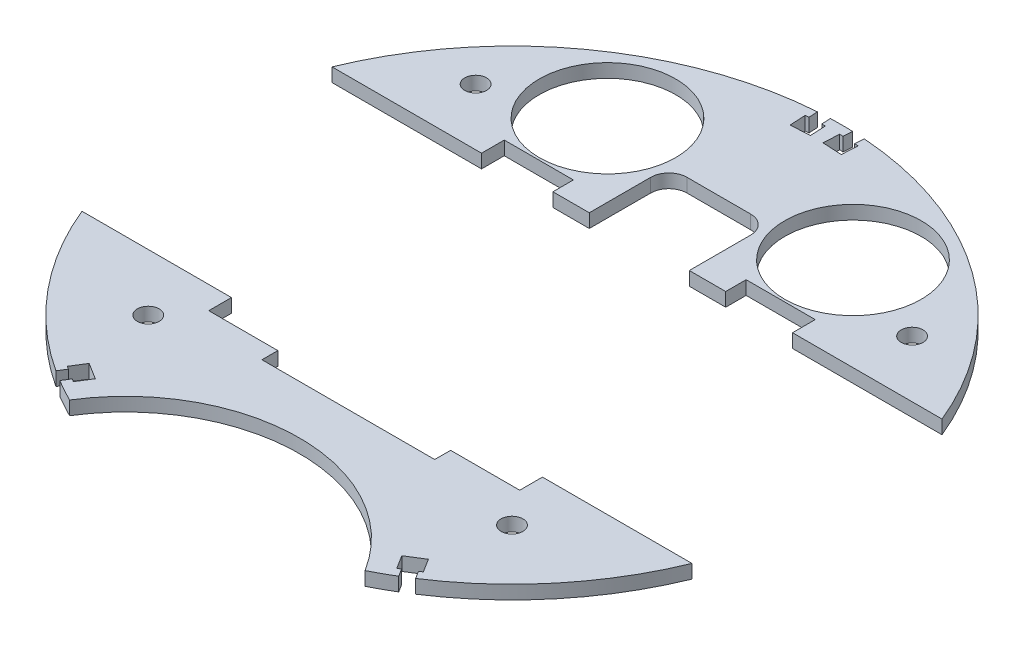
SolidWorks part; units mm, degrees
material "ABS"
ref_plane "Front Plane" through (0, 0, 0) normal (0, 0, 1) x (1, 0, 0)
ref_plane "Top Plane" through (0, 0, 0) normal (0, 1, 0) x (1, 0, 0)
ref_plane "Right Plane" through (0, 0, 0) normal (1, 0, 0) x (0, 0, -1)
sketch "Sketch1" plane through (0, 0, 0) normal (0, 1, 0) x (1, 0, 0)
  line L0 (0, -85) -> (-32.4891, -64.8129) construction
  line L1 (0, -85) -> (0, 0) construction
  arc A0 (32.4891, -64.8129) -> (-32.4891, -64.8129) centre (0, 0) ccw
  arc A1 (32.4891, -64.8129) -> (-32.4891, -64.8129) centre (0, -85) ccw
  dimension "D1" = 145
  dimension "D2" = 76.5
  dimension "D3" = 85
extrude "Boss-Extrude1" add sketch "Sketch1" along normal blind 3
sketch "solenoid placement" plane through (0, 3, 0) normal (0, 1, 0) x (1, 0, 0)
  line L4 (-19, -36) -> (19, -36)
  line L5 (-19, -36) -> (19, -36)
  line L6 (19, -36) -> (19, 28)
  line L7 (19, -36) -> (19, 28)
  line L8 (19, 28) -> (-19, 28)
  line L9 (19, 28) -> (-19, 28)
  line L10 (-19, 28) -> (-19, -36)
  line L11 (-19, 28) -> (-19, -36)
  circle A1 centre (0, 0) radius 72.5 construction
  arc A2 (32.4891, -64.8129) -> (-32.4891, -64.8129) centre (0, 0) ccw construction
  dimension "D1" = 0
extrude "Cut-Extrude1" cut sketch "solenoid placement" against normal through all
sketch "Sketch3" plane through (0, 3, 0) normal (0, 1, 0) x (1, 0, 0)
  circle A1 centre (27, 48) radius 12
  circle A2 centre (-27, 48) radius 12
  dimension "D1" = 24
extrude "Cut-Extrude3" cut sketch "Sketch3" against normal through all
sketch "Sketch4" plane through (0, 3, 0) normal (0, 1, 0) x (1, 0, 0)
  circle A2 centre (40, -40) radius 2.4
  circle A3 centre (40, -40) radius 2.4
  circle A4 centre (-40, -40) radius 2.4
  circle A5 centre (-40, -40) radius 2.4
  circle A6 centre (48, 40) radius 2.4
  circle A7 centre (48, 40) radius 2.4
  circle A8 centre (-48, 40) radius 2.4
  circle A12 centre (-48, 40) radius 2.4
  dimension "D1" = 0
  dimension "D2" = 0
  dimension "D3" = 0
  dimension "D4" = 0
extrude "Cut-Extrude4" cut sketch "Sketch4" against normal through all
sketch "Sketch2" plane through (0, 3, 0) normal (0, 1, 0) x (1, 0, 0)
  line L0 (0, 0) -> (0, 72.5) construction
  line L1 (34.2, -27.5) -> (34.2, -32.5)
  line L2 (67.082, -27.5) -> (34.2, -27.5)
  line L3 (34.2, 27.5) -> (67.082, 27.5)
  line L4 (34.2, 32.5) -> (34.2, 27.5)
  line L5 (22.2, 32.5) -> (34.2, 32.5)
  line L6 (19, 32.5) -> (22.2, 32.5)
  line L7 (19, -32.5) -> (19, 32.5)
  line L8 (22.2, -32.5) -> (19, -32.5)
  line L9 (-34.2, -32.5) -> (-22.2, -32.5)
  line L10 (-22.2, -32.5) -> (-19, -32.5)
  line L11 (-19, -32.5) -> (-19, 32.5)
  line L12 (-19, 32.5) -> (-22.2, 32.5)
  line L13 (-22.2, 32.5) -> (-34.2, 32.5)
  line L14 (-34.2, 32.5) -> (-34.2, 25)
  line L15 (-34.2, 25) -> (-68.0533, 25)
  line L16 (-68.0533, -25) -> (-34.2, -25)
  line L17 (-34.2, -25) -> (-34.2, -32.5)
  line L18 (-34.2, -32.5) -> (-22.2, -32.5)
  line L19 (-22.2, -32.5) -> (-19, -32.5)
  line L20 (-19, -32.5) -> (-19, 32.5)
  line L21 (-19, 32.5) -> (-22.2, 32.5)
  line L22 (-22.2, 32.5) -> (-34.2, 32.5)
  line L23 (-34.2, 32.5) -> (-34.2, 27.5)
  line L24 (-34.2, 27.5) -> (-67.082, 27.5)
  line L25 (-67.082, -27.5) -> (-34.2, -27.5)
  line L26 (-34.2, -27.5) -> (-34.2, -32.5)
  line L27 (34.2, -32.5) -> (22.2, -32.5)
  arc A0 (32.4891, -64.8129) -> (-32.4891, -64.8129) centre (0, 0) ccw construction
  arc A1 (67.082, 27.5) -> (67.082, -27.5) centre (0, 0) cw
  arc A2 (-68.0533, 25) -> (-68.0533, -25) centre (0, 0) ccw
  arc A3 (-67.082, 27.5) -> (-67.082, -27.5) centre (0, 0) ccw
  dimension "D2" = 55
  dimension "D1" = 0
extrude "Cut-Extrude2" cut sketch "Sketch2" against normal through all
sketch "Sketch5" plane through (0, 3, 0) normal (0, 1, 0) x (1, 0, 0)
  line L8 (-11, 28) -> (11, 28)
  line L9 (11, 28) -> (11, 41.5)
  line L10 (7, 45.5) -> (-7, 45.5)
  line L11 (-11, 41.5) -> (-11, 28)
  line L12 (19, 28) -> (-19, 28) construction
  arc A4 (11, 41.5) -> (7, 45.5) centre (7, 41.5) ccw
  arc A5 (-7, 45.5) -> (-11, 41.5) centre (-7, 41.5) ccw
  point P10 (0, 28)
  point P13 (0, 28)
  line M18 (-19, 28) -> (19, 28)
  dimension "D3" = 4
  dimension "D1" = 22
  dimension "D2" = 17.5
extrude "Cut-Extrude5" cut sketch "Sketch5" against normal through all contours L10 A5 L11 L9 A4 M18 region at (0, 3, -36.6073)
sketch "Sketch6" plane through (0, 3, 0) normal (0, 1, 0) x (-1, 0, 0)
  circle A1 centre (-27, -48) radius 15
  circle A2 centre (-27, -48) radius 15
  circle A3 centre (27, -48) radius 15
  circle A4 centre (27, -48) radius 15
  dimension "D1" = 0
  dimension "D2" = 0
extrude "Cut-Extrude10" cut sketch "Sketch6" against normal through all
sketch "Sketch7" plane through (0, 3, 0) normal (0, 1, 0) x (1, 0, 0)
  line L8 (-5.0378, 70.3327) -> (-5.8118, 70.2922)
  line L9 (-5.8118, 70.2922) -> (-5.6286, 66.797)
  line L10 (-5.6286, 66.797) -> (-1.3844, 67.0194)
  line L11 (-1.3844, 67.0194) -> (-1.5676, 70.5146)
  line L12 (-1.5676, 70.5146) -> (-2.3415, 70.474)
  line L13 (-2.3415, 70.474) -> (-2.4462, 72.4713)
  line L14 (-2.4462, 72.4713) -> (-5.1425, 72.33)
  line L15 (-5.1425, 72.33) -> (-5.0378, 70.3327)
  line L16 (-5.0378, 70.3327) -> (-5.8118, 70.2922)
  line L17 (-5.8118, 70.2922) -> (-5.6286, 66.797)
  line L18 (-5.6286, 66.797) -> (-1.3844, 67.0194)
  line L19 (-1.3844, 67.0194) -> (-1.5676, 70.5146)
  line L20 (-1.5676, 70.5146) -> (-2.3415, 70.474)
  line L21 (-2.3415, 70.474) -> (-2.4462, 72.4713)
  line L22 (-2.4462, 72.4713) -> (-5.1425, 72.33)
  line L23 (-5.1425, 72.33) -> (-5.0378, 70.3327)
  line L24 (5.8118, 70.2922) -> (5.0378, 70.3327)
  line L25 (5.6286, 66.797) -> (5.8118, 70.2922)
  line L26 (1.3844, 67.0194) -> (5.6286, 66.797)
  line L27 (1.5676, 70.5146) -> (1.3844, 67.0194)
  line L28 (2.3415, 70.474) -> (1.5676, 70.5146)
  line L29 (2.4462, 72.4713) -> (2.3415, 70.474)
  line L30 (5.1425, 72.33) -> (2.4462, 72.4713)
  line L31 (5.0378, 70.3327) -> (5.1425, 72.33)
  line L32 (5.8118, 70.2922) -> (5.0378, 70.3327)
  line L33 (5.6286, 66.797) -> (5.8118, 70.2922)
  line L34 (1.3844, 67.0194) -> (5.6286, 66.797)
  line L35 (1.5676, 70.5146) -> (1.3844, 67.0194)
  line L36 (2.3415, 70.474) -> (1.5676, 70.5146)
  line L37 (2.4462, 72.4713) -> (2.3415, 70.474)
  line L38 (5.1425, 72.33) -> (2.4462, 72.4713)
  line L39 (5.0378, 70.3327) -> (5.1425, 72.33)
  line L40 (38.5042, -59.072) -> (39.1614, -58.6613)
  line L41 (39.564, -60.7681) -> (38.5042, -59.072)
  line L42 (37.2743, -62.1989) -> (39.564, -60.7681)
  line L43 (36.2144, -60.5028) -> (37.2743, -62.1989)
  line L44 (35.5572, -60.9135) -> (36.2144, -60.5028)
  line L45 (33.7025, -57.9453) -> (35.5572, -60.9135)
  line L46 (37.3067, -55.6931) -> (33.7025, -57.9453)
  line L47 (39.1614, -58.6613) -> (37.3067, -55.6931)
  line L48 (38.5042, -59.072) -> (39.1614, -58.6613)
  line L49 (39.564, -60.7681) -> (38.5042, -59.072)
  line L50 (37.2743, -62.1989) -> (39.564, -60.7681)
  line L51 (36.2144, -60.5028) -> (37.2743, -62.1989)
  line L52 (35.5572, -60.9135) -> (36.2144, -60.5028)
  line L53 (33.7025, -57.9453) -> (35.5572, -60.9135)
  line L54 (37.3067, -55.6931) -> (33.7025, -57.9453)
  line L55 (39.1614, -58.6613) -> (37.3067, -55.6931)
  line L56 (-39.1614, -58.6613) -> (-38.5042, -59.072)
  line L57 (-37.3067, -55.6931) -> (-39.1614, -58.6613)
  line L58 (-33.7025, -57.9453) -> (-37.3067, -55.6931)
  line L59 (-35.5572, -60.9135) -> (-33.7025, -57.9453)
  line L60 (-36.2144, -60.5028) -> (-35.5572, -60.9135)
  line L61 (-37.2743, -62.1989) -> (-36.2144, -60.5028)
  line L62 (-39.564, -60.7681) -> (-37.2743, -62.1989)
  line L63 (-38.5042, -59.072) -> (-39.564, -60.7681)
  line L64 (-39.1614, -58.6613) -> (-38.5042, -59.072)
  line L65 (-37.3067, -55.6931) -> (-39.1614, -58.6613)
  line L66 (-33.7025, -57.9453) -> (-37.3067, -55.6931)
  line L67 (-35.5572, -60.9135) -> (-33.7025, -57.9453)
  line L68 (-36.2144, -60.5028) -> (-35.5572, -60.9135)
  line L69 (-37.2743, -62.1989) -> (-36.2144, -60.5028)
  line L70 (-39.564, -60.7681) -> (-37.2743, -62.1989)
  line L71 (-38.5042, -59.072) -> (-39.564, -60.7681)
  dimension "D1" = 0
  dimension "D2" = 0
  dimension "D3" = 0
  dimension "D4" = 0
extrude "Cut-Extrude11" cut sketch "Sketch7" against normal through all
sketch "Sketch8" plane through (0, 3, 0) normal (0, 1, 0) x (1, 0, 0)
  line L2 (7, 48.5) -> (-7, 48.5)
  line L3 (7.1569, 48.5) -> (-7.1569, 48.5)
  line L8 (-8.4675, 63.6441) -> (-1.2274, 64.0235)
  line L9 (-8.8077, 70.1352) -> (-8.4675, 63.6441)
  line L10 (-6.4702, 63.7487) -> (-0.1047, 64.0823)
  line L11 (-8.6309, 66.7627) -> (-8.5721, 65.6413)
  line L15 (8.4675, 63.6441) -> (8.8077, 70.1352)
  line L16 (1.2274, 64.0235) -> (8.4675, 63.6441)
  line L17 (8.5721, 65.6413) -> (8.6309, 66.7627)
  line L18 (0.1047, 64.0823) -> (6.4702, 63.7487)
  circle A2 centre (-27, 48) radius 18
  arc A3 (-9.1412, 50.25) -> (-18.004, 63.5907) centre (-27, 48) ccw
  circle A5 centre (27, 48) radius 18
  arc A6 (18.004, 63.5907) -> (9.1412, 50.25) centre (27, 48) ccw
  arc A8 (-4.9291, 69.325) -> (-64.3062, 26.3621) centre (0, 0) ccw
  arc A9 (-10.9431, 68.6331) -> (-17.5082, 67.2585) centre (0, 0) ccw
  arc A10 (17.5082, 67.2585) -> (10.9431, 68.6331) centre (0, 0) ccw
  arc A11 (-9.1412, 50.25) -> (-7.1569, 48.5) centre (-7.1569, 50.5) ccw
  arc A12 (9.1412, 50.25) -> (7.1569, 48.5) centre (7.1569, 50.5) cw
  arc A13 (17.5082, 67.2585) -> (18.004, 63.5907) centre (17.0044, 65.323) cw
  arc A14 (10.9431, 68.6331) -> (8.6309, 66.7627) centre (10.6282, 66.658) ccw
  arc A15 (8.5721, 65.6413) -> (6.4702, 63.7487) centre (6.5749, 65.746) cw
  arc A16 (-0.1047, 64.0823) -> (0.1047, 64.0823) centre (0, 62.0851) cw
  arc A17 (-6.4702, 63.7487) -> (-8.5721, 65.6413) centre (-6.5749, 65.746) cw
  arc A18 (-8.6309, 66.7627) -> (-10.9431, 68.6331) centre (-10.6282, 66.658) ccw
  arc A19 (-18.004, 63.5907) -> (-17.5082, 67.2585) centre (-17.0044, 65.323) cw
  dimension "D5" = 2
  dimension "D1" = 3
  dimension "D2" = 3
  dimension "D3" = 3
  dimension "D4" = 3
  dimension "D6" = 3
  dimension "D7" = 3
extrude "Cut-Extrude12" [suppressed] cut sketch "Sketch8" against normal through all and the other way through all
equation "\"smallPulleyTeeth\"= 15"
equation "\"largePulleyTeeth\"= 30"
equation "\"eighthThick\"= 3.0mm"
equation "\"sixteenthThick\"= 1.7mm"
equation "\"quarterThick\"=6.0mm"
equation "\"OD\"= 145mm"
equation "\"puckAngle\"= 60.5deg"
equation "\"D1@Sketch1\"=\"OD\""
equation "\"puckDiam\"= 76.5mm"
equation "\"D2@Sketch1\"=\"puckDiam\""
equation "\"D1@Boss-Extrude1\"=\"eighthThick\""
equation "\"axlePress\"= 5.9mm"
equation "\"press\"= 0.2mm"
equation "\"wheelClear\"= 0.3mm"
equation "\"10-32clear\"= 4.8mm"
equation "\"6-32clear\"= 3.3mm"
equation "\"8-32clear\"= 4.0mm"
equation "\"wheelHeight\"= 22mm"
equation "\"wheelWell\"= 65mm"
equation "\"puckDist\"= 85mm"
equation "\"scoopFillet\"= 5mm"
equation "\"4-40clear\"= 3.0mm"
equation "\"D3@Sketch1\"=\"puckDist\""
